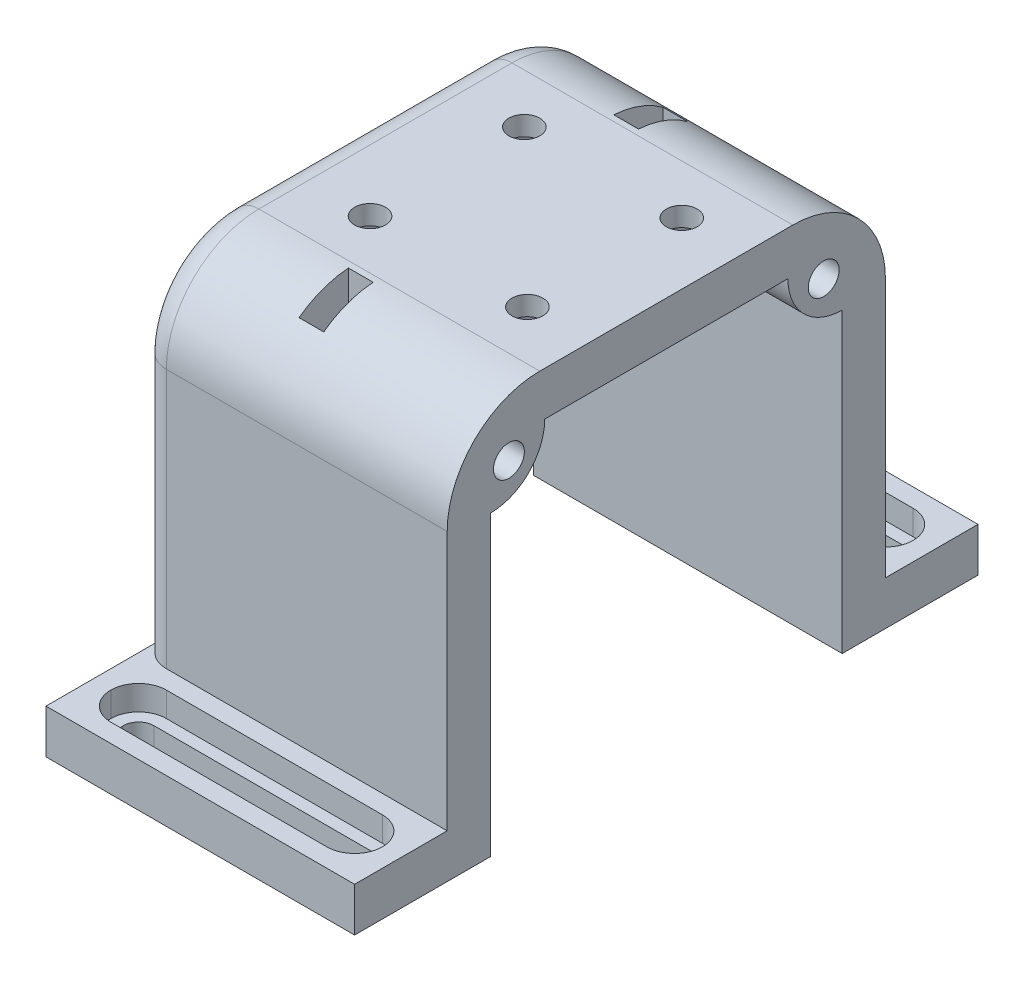
SolidWorks part; units mm, degrees
ref_plane "Front Plane" through (0, 0, 0) normal (0, 0, 1) x (1, 0, 0)
ref_plane "Top Plane" through (0, 0, 0) normal (0, 1, 0) x (1, 0, 0)
ref_plane "Right Plane" through (0, 0, 0) normal (1, 0, 0) x (0, 0, -1)
sketch "Sketch1" plane through (0, 0, 0) normal (1, 0, 0) x (0, 0, -1)
  line L5 (-28.5, 28.5) -> (28.5, -28.5) construction
  line L6 (-28.5, -28.5) -> (28.5, 28.5) construction
  line L7 (35.5, 35.6293) -> (-35.5, 35.6293)
  line L8 (-35.5, 35.6293) -> (-35.5, -21.3707)
  line L9 (-35.5, -21.3707) -> (-50.5, -21.3707)
  line L10 (-50.5, -21.3707) -> (-50.5, -28.5)
  line L11 (-50.5, -28.5) -> (-28.5, -28.5)
  line L12 (-28.5, -28.5) -> (-28.5, 19.7)
  line L13 (19.7, 28.5) -> (-19.7, 28.5)
  line L14 (50.5, -21.3707) -> (50.5, -28.5)
  line L15 (35.5, -21.3707) -> (50.5, -21.3707)
  line L16 (35.5, 35.6293) -> (35.5, -21.3707)
  line L17 (28.5, -28.5) -> (28.5, 19.7)
  line L18 (50.5, -28.5) -> (28.5, -28.5)
  arc A1 (-28.5, 19.7) -> (-19.7, 28.5) centre (-28.5, 28.5) ccw
  arc A2 (28.5, 19.7) -> (19.7, 28.5) centre (28.5, 28.5) cw
  point P0 (0, 0)
  dimension "D5" = 15
  dimension "D1" = 57
  dimension "D2" = 57
extrude "Boss-Extrude1" add sketch "Sketch1" along normal blind 50
sketch "Sketch2" plane through (0, 0, 0) normal (-1, 0, 0) x (0, 0, 1)
  line L0 (-35.5, 35.6293) -> (0, 0) construction
  line L1 (-28.5, 19.7) -> (-28.5, -28.5) construction
  line L2 (0, 42.4806) -> (0, -25.1676) construction
  line L3 (-35.5, -21.3707) -> (-35.5, 35.6293) construction
  circle A0 centre (-25.5, 25.5929) radius 2.5
  circle A2 centre (25.5, 25.5929) radius 2.5
  dimension "D1" = 5
  dimension "D2" = 3
  dimension "D3" = 10
extrude "Cut-Extrude1" cut sketch "Sketch2" against normal blind 50
fillet "Fillet1" radius 15 2 edges at (25, 35.6293, 35.5) (25, 35.6293, -35.5)
sketch "Sketch3" plane through (0, 35.6293, 0) normal (0, 1, 0) x (1, 0, 0)
  line L1 (20, 29.5) -> (24, 29.5)
  line L2 (20, 29.5) -> (20, 21.5)
  line L3 (20, 21.5) -> (24, 21.5)
  line L4 (24, 29.5) -> (24, 21.5)
  line L5 (-4.4176, 0) -> (51.6177, 0) construction
  line L6 (20, -21.5) -> (24, -21.5)
  line L7 (24, -29.5) -> (24, -21.5)
  line L8 (20, -29.5) -> (24, -29.5)
  line L17 (20, -29.5) -> (20, -21.5)
  dimension "D1" = 8
  dimension "D2" = 4
extrude "Cut-Extrude2" cut sketch "Sketch3" against normal blind 14.54
sketch "Sketch4" plane through (0, -21.3707, 0) normal (0, 1, 0) x (1, 0, 0)
  line L6 (0, -35.5) -> (50, -50.5) construction
  line L7 (50, -35.5) -> (0, -50.5) construction
  line L9 (3, -38.5) -> (47, -38.5)
  line L10 (3, -38.5) -> (3, -47.5)
  line L11 (3, -47.5) -> (47, -47.5)
  line L12 (47, -38.5) -> (47, -47.5)
  line L13 (3, -38.5) -> (47, -47.5) construction
  line L14 (3, -47.5) -> (47, -38.5) construction
  line L15 (50, -35.5) -> (50, -50.5) construction
  line L16 (-1.8281, 0) -> (54.8376, 0) construction
  line L17 (3, 47.5) -> (47, 47.5)
  line L18 (47, 38.5) -> (47, 47.5)
  line L19 (3, 38.5) -> (47, 38.5)
  line L20 (3, 38.5) -> (3, 47.5)
  point P4 (25, -43)
  dimension "D1" = 9
  dimension "D2" = 3
extrude "Cut-Extrude3" cut sketch "Sketch4" against normal blind 4
sketch "Sketch5" plane through (0, -25.3707, 0) normal (0, 1, 0) x (1, 0, 0)
  line L0 (3, -38.5) -> (47, -47.5) construction
  line L1 (47, -47.5) -> (47, -38.5) construction
  line L2 (47, -38.5) -> (3, -47.5) construction
  line L4 (5, -40.5) -> (45, -40.5)
  line L5 (5, -40.5) -> (5, -45.5)
  line L6 (5, -45.5) -> (45, -45.5)
  line L7 (45, -40.5) -> (45, -45.5)
  line L8 (5, -40.5) -> (45, -45.5) construction
  line L9 (5, -45.5) -> (45, -40.5) construction
  line L10 (3, -38.5) -> (3, -47.5) construction
  line L11 (-1.2266, 0) -> (55.9736, 0) construction
  line L12 (5, 45.5) -> (45, 45.5)
  line L13 (45, 40.5) -> (45, 45.5)
  line L14 (5, 40.5) -> (45, 40.5)
  line L15 (5, 40.5) -> (5, 45.5)
  point P4 (25, -43)
  dimension "D1" = 5
  dimension "D2" = 2
extrude "Cut-Extrude4" cut sketch "Sketch5" against normal through all
fillet "Fillet2" radius 2.5 8 edges at (45, -26.9353, 40.5) (45, -26.9353, 45.5) (5, -26.9353, 45.5) (5, -26.9353, 40.5) (5, -26.9353, -45.5) (5, -26.9353, -40.5) (45, -26.9353, -45.5) (45, -26.9353, -40.5)
fillet "Fillet3" radius 4.5 8 edges at (3, -23.3707, 38.5) (3, -23.3707, 47.5) (47, -23.3707, 47.5) (47, -23.3707, 38.5) (47, -23.3707, -47.5) (47, -23.3707, -38.5) (3, -23.3707, -47.5) (3, -23.3707, -38.5)
fillet "Fillet4" radius 4.5 5 edges at (0, -0.3707, -35.5) (0, 31.2359, -31.1066) (0, -0.3707, 35.5) (0, 31.2359, 31.1066) (0, 35.6293, 0)
sketch "Sketch6" plane through (0, 35.6293, 0) normal (0, 1, 0) x (1, 0, 0)
  line L0 (4.5, 0) -> (50, 0) construction
  line L1 (4.5, 20.5) -> (4.5, -20.5) construction
  line L2 (50, 20.5) -> (50, -20.5) construction
  line L3 (16.8094, -8.5) -> (19.1188, -12.5)
  line L8 (14.5, 12.5) -> (40, -12.5) construction
  line L9 (14.5, -12.5) -> (40, 12.5) construction
  line L10 (19.1188, 12.5) -> (16.8094, 16.5)
  line L11 (16.8094, 16.5) -> (12.1906, 16.5)
  line L12 (12.1906, 16.5) -> (9.8812, 12.5)
  line L13 (9.8812, 12.5) -> (12.1906, 8.5)
  line L14 (12.1906, 8.5) -> (16.8094, 8.5)
  line L15 (16.8094, 8.5) -> (19.1188, 12.5)
  line L16 (12.1906, -8.5) -> (16.8094, -8.5)
  line L17 (9.8812, -12.5) -> (12.1906, -8.5)
  line L18 (12.1906, -16.5) -> (9.8812, -12.5)
  line L19 (16.8094, -16.5) -> (12.1906, -16.5)
  line L20 (19.1188, -12.5) -> (16.8094, -16.5)
  line L21 (27.25, 15.7448) -> (27.25, -16.0563) construction
  line L22 (42.3094, -8.5) -> (37.6906, -8.5)
  line L23 (44.6188, -12.5) -> (42.3094, -8.5)
  line L24 (42.3094, -16.5) -> (44.6188, -12.5)
  line L25 (37.6906, -16.5) -> (42.3094, -16.5)
  line L26 (35.3812, -12.5) -> (37.6906, -16.5)
  line L27 (37.6906, -8.5) -> (35.3812, -12.5)
  line L28 (37.6906, 8.5) -> (35.3812, 12.5)
  line L29 (42.3094, 8.5) -> (37.6906, 8.5)
  line L30 (44.6188, 12.5) -> (42.3094, 8.5)
  line L31 (42.3094, 16.5) -> (44.6188, 12.5)
  line L32 (37.6906, 16.5) -> (42.3094, 16.5)
  line L33 (35.3812, 12.5) -> (37.6906, 16.5)
  circle A0 centre (14.5, 12.5) radius 4 construction
  circle A1 centre (14.5, 12.5) radius 2.5
  circle A2 centre (40, 12.5) radius 2.5
  circle A3 centre (40, -12.5) radius 2.5
  circle A4 centre (14.5, -12.5) radius 2.5
  point P9 (27.25, 0)
  dimension "D3" = 10
  dimension "D1" = 25
  dimension "D2" = 8
extrude "Cut-Extrude5" cut sketch "Sketch6" along normal blind 4 from surface starting at face at (25, 28.5, 0)
sketch "Sketch8" plane through (0, 28.5, 0) normal (0, -1, 0) x (1, 0, 0)
  circle A0 centre (14.5, -12.5) radius 2.5 construction
  circle A1 centre (40, 12.5) radius 2.5 construction
  circle A2 centre (14.5, 12.5) radius 2.5 construction
  circle A3 centre (40, -12.5) radius 2.5 construction
  circle A4 centre (14.5, -12.5) radius 2.5
  circle A5 centre (40, 12.5) radius 2.5
  circle A6 centre (14.5, 12.5) radius 2.5
  circle A7 centre (40, -12.5) radius 2.5
extrude "Cut-Extrude6" cut sketch "Sketch8" against normal through all
